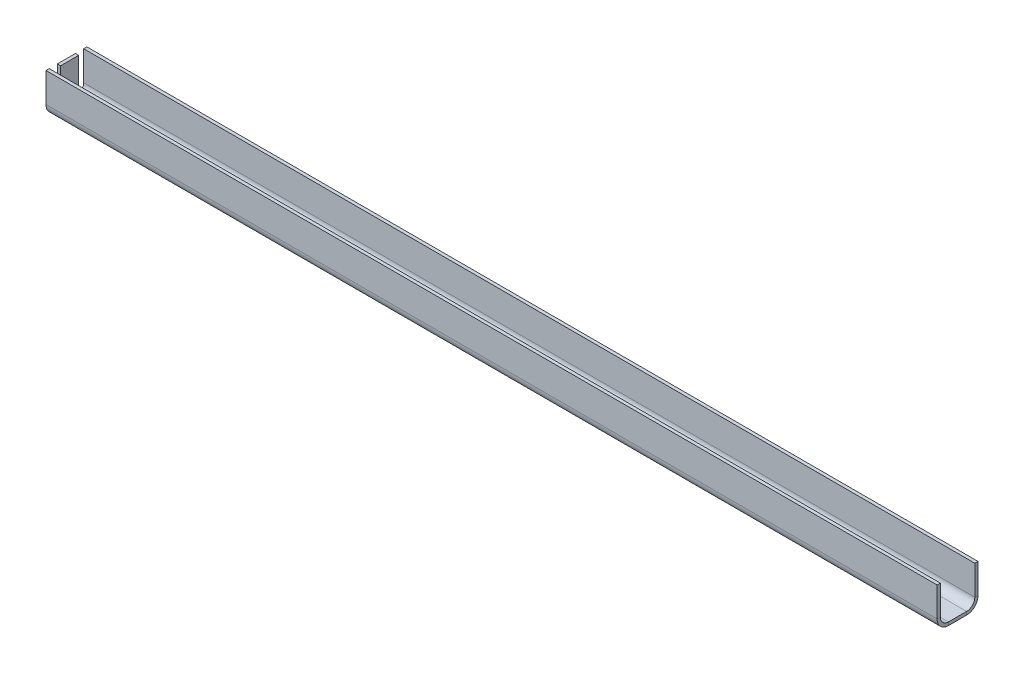
SolidWorks part; units mm, degrees
note: The reader was unsure of these and kept them because the rebuilt part matched: flange length of "Edge-Flange1", "Edge-Flange2", "Edge-Flange3".
ref_plane "Front Plane" through (0, 0, 0) normal (0, 0, 1) x (1, 0, 0)
ref_plane "Top Plane" through (0, 0, 0) normal (0, 1, 0) x (1, 0, 0)
ref_plane "Right Plane" through (0, 0, 0) normal (1, 0, 0) x (0, 0, -1)
sketch "Sketch10" plane through (0, 0, 0) normal (0, 1, 0) x (1, 0, 0)
  line L1 (-138.43, -6.35) -> (138.43, -6.35)
  line L2 (-138.43, -6.35) -> (-138.43, 6.35)
  line L3 (-138.43, 6.35) -> (138.43, 6.35)
  line L4 (138.43, -6.35) -> (138.43, 6.35)
  line L5 (-138.43, -6.35) -> (138.43, 6.35) construction
  line L6 (-138.43, 6.35) -> (138.43, -6.35) construction
  point P0 (0, 0)
  dimension "D1" = 276.86
  dimension "D2" = 12.7
base flange "Base-Flange1" sketch "Sketch10" thickness 1 reverse thickness direction no parameters "D1"=6.35
sketch "Sketch15" plane through (0, 0, 6.35) normal (0, 0, 1) x (1, 0, 0)
  line L1 (-138.43, -1) -> (138.4276, -1)
  line L2 (-138.43, -1) -> (-138.43, 11.7)
  line L3 (-138.43, 11.7) -> (138.4276, 11.7)
  line L4 (138.4276, -1) -> (138.4276, 11.7)
  dimension "D1" = 12.7
edge flange "Edge-Flange1" sketch "Sketch22" flange angle 90 flange length 12.7 flange position material inside bend radius 2.54 thickness 1 relief rectangular parameters "D6"=10
sketch "Sketch22" plane through (0, 0, -6.35) normal (0, 0, -1) x (-1, 0, 0)
  line L2 (-138.43, 0) -> (-138.43, 11.7)
  line L3 (-138.43, 11.7) -> (138.43, 11.7)
  line L4 (138.43, 11.7) -> (138.43, 0)
  line L5 (-138.43, 0) -> (138.43, 0) construction
  line L6 (-138.43, 0) -> (138.43, 0)
bend "EdgeBend1" bend radius 2.54 bend angle 90 parameters "D5"=1
edge flange "Edge-Flange2" sketch "Sketch25" flange angle 90 flange length 12.7 flange position material inside bend radius 2.54 thickness 1 relief rectangular parameters "D6"=10
sketch "Sketch25" plane through (0, 0, 6.35) normal (0, 0, 1) x (1, 0, 0)
  line L2 (-138.43, 0) -> (-138.43, 11.7)
  line L3 (-138.43, 11.7) -> (138.43, 11.7)
  line L4 (138.43, 11.7) -> (138.43, 0)
  line L5 (-138.43, 0) -> (138.43, 0) construction
  line L6 (-138.43, 0) -> (138.43, 0)
bend "EdgeBend2" bend radius 2.54 bend angle 90 parameters "D5"=2
edge flange "Edge-Flange3" sketch "Sketch28" flange angle 90 flange length 12.7 flange position material inside bend radius 2.54 thickness 1 relief none parameters "D6"=10
sketch "Sketch28" plane through (-138.43, 0, 0) normal (-1, 0, 0) x (0, 0, 1)
  line L2 (-2.81, 0) -> (-2.81, 11.7)
  line L3 (-2.81, 11.7) -> (2.81, 11.7)
  line L4 (2.81, 11.7) -> (2.81, 0)
  line L5 (-2.81, 0) -> (2.81, 0) construction
  line L6 (-2.81, 0) -> (2.81, 0)
bend "EdgeBend3" bend radius 2.54 bend angle 90 parameters "D5"=3
sketch "Bend-Lines5" plane through (0, 0, 0) normal (0, 1, 0) x (1, 0, 0)
sketch "Bounding-Box5" plane through (0, 0, 0) normal (0, 1, 0) x (1, 0, 0)
sheet metal parameters "Sheet-Metal4" thickness 1 parameters "D1"=6.35
flat pattern "Flat-Pattern4" [suppressed]
sketch "Bend-Lines6" plane through (0, 0, 0) normal (0, 1, 0) x (1, 0, 0)
sketch "Bounding-Box6" [suppressed] plane through (0, 0, 0) normal (0, 1, 0) x (1, 0, 0)
sheet metal parameters "Sheet-Metal6" thickness 1 parameters "D1"=6.35
flat pattern "Flat-Pattern4" [suppressed]
sketch "Bend-Lines6" plane through (0, 0, 0) normal (0, 1, 0) x (1, 0, 0)
sketch "Bounding-Box6" [suppressed] plane through (0, 0, 0) normal (0, 1, 0) x (1, 0, 0)
bend of the flat pattern "Flatten-<EdgeBend1>1"
sheet metal parameters "Sheet-Metal7" thickness 1 parameters "D1"=6.35
flat pattern "Flat-Pattern4" [suppressed]
sketch "Bend-Lines6" plane through (0, 0, 0) normal (0, 1, 0) x (1, 0, 0)
sketch "Bounding-Box6" [suppressed] plane through (0, 0, 0) normal (0, 1, 0) x (1, 0, 0)
bend of the flat pattern "Flatten-<EdgeBend1>1"
bend of the flat pattern "Flatten-<EdgeBend2>1"
sheet metal parameters "Sheet-Metal8" thickness 1 parameters "D1"=6.35
flat pattern "Flat-Pattern4" [suppressed]
sketch "Bend-Lines6" plane through (0, 0, 0) normal (0, 1, 0) x (1, 0, 0)
sketch "Bounding-Box6" [suppressed] plane through (0, 0, 0) normal (0, 1, 0) x (1, 0, 0)
bend of the flat pattern "Flatten-<EdgeBend1>1"
bend of the flat pattern "Flatten-<EdgeBend2>1"
bend of the flat pattern "Flatten-<EdgeBend3>1"
